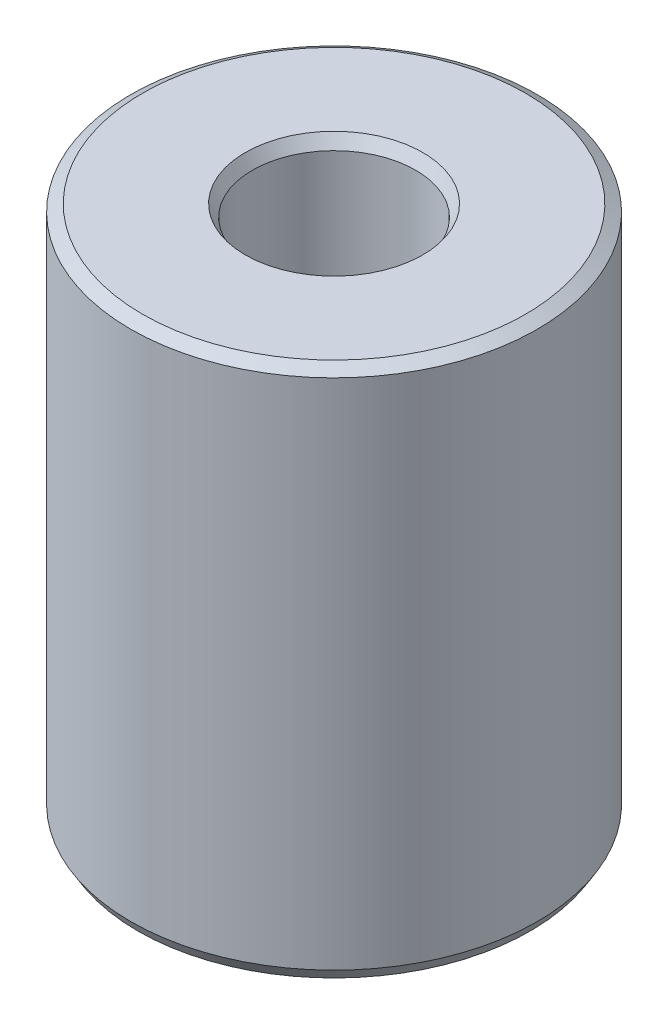
SolidWorks part; units mm, degrees
ref_plane "Front Plane" through (0, 0, 0) normal (0, 0, 1) x (1, 0, 0)
ref_plane "Top Plane" through (0, 0, 0) normal (0, 1, 0) x (1, 0, 0)
ref_plane "Right Plane" through (0, 0, 0) normal (1, 0, 0) x (0, 0, -1)
sketch "Sketch1" plane through (0, 0, 0) normal (0, 1, 0) x (1, 0, 0)
  circle A0 centre (0, 0) radius 22.5
  dimension "SLEEVE_OD" = 45
extrude "Boss-Extrude1" add sketch "Sketch1" along normal blind 58.8667
sketch "Sketch2" plane through (0, 0, 0) normal (0, 1, 0) x (1, 0, 0)
  circle A0 centre (0, 0) radius 9.039
  dimension "BORE_D" = 18.078
extrude "Cut-Extrude1" cut sketch "Sketch2" along normal through all
chamfer "Chamfer1" distance 0.7852 angle 58.944 4 edges at (0, 58.8667, 9.039) (0, 0, 9.039) (0, 0, 22.5) (0, 58.8667, 22.5) first distance on face at (0, 58.8667, 9.039) first distance on face at (0, 0, 9.039) first distance on face at (0, 58.8667, 22.5)
